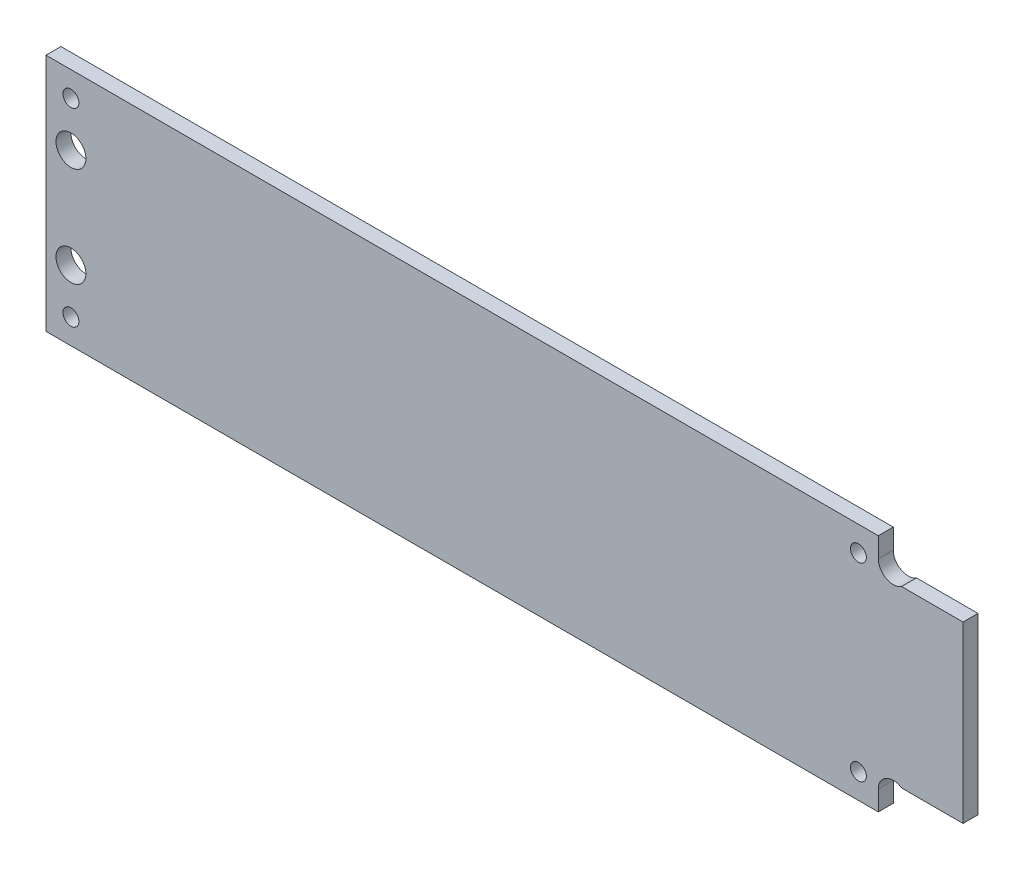
SolidWorks part; units mm, degrees
ref_plane "Top Plane" through (0, 0, 0) normal (0, 0, 1) x (1, 0, 0)
ref_plane "Right Plane" through (0, 0, 0) normal (0, 1, 0) x (1, 0, 0)
ref_plane "Front Plane" through (0, 0, 0) normal (1, 0, 0) x (0, 0, -1)
sketch "Sketch1" plane through (0, 0, 0) normal (0, 0, 1) x (1, 0, 0)
  line L8 (87.6583, -17.5) -> (100, -17.5)
  line L9 (100, -17.5) -> (100, 17.5)
  line L10 (100, 17.5) -> (87.6583, 17.5)
  line L11 (83, 20) -> (83, 24)
  line L12 (83, 24) -> (-84, 24)
  line L13 (-84, 24) -> (-84, -24)
  line L14 (-84, -24) -> (83, -24)
  line L15 (83, -24) -> (83, -20)
  line L16 (87.6583, -17.5) -> (100, -17.5)
  line L17 (100, -17.5) -> (100, 17.5)
  line L18 (100, 17.5) -> (87.6583, 17.5)
  line L19 (83, 20) -> (83, 24)
  line L20 (83, 24) -> (-84, 24)
  line L21 (-84, 24) -> (-84, -24)
  line L22 (-84, -24) -> (83, -24)
  line L23 (83, -24) -> (83, -20)
  line L36 (77, 10) -> (74, 10)
  line L37 (77, 15.5) -> (77, 10)
  line L38 (98, 15.5) -> (77, 15.5)
  line L39 (98, -15.5) -> (98, 15.5)
  line L40 (77, -15.5) -> (98, -15.5)
  line L41 (77, -10) -> (77, -15.5)
  line L42 (74, -10) -> (77, -10)
  line L43 (74, -20) -> (74, -10)
  line L44 (6, -21) -> (73, -21)
  line L45 (5, -19) -> (5, -20)
  line L46 (-5, -20) -> (-5, -19)
  line L47 (-73, -21) -> (-6, -21)
  line L48 (-74, 20) -> (-74, -20)
  line L49 (-6, 21) -> (-73, 21)
  line L50 (-5, 19) -> (-5, 20)
  line L51 (5, 20) -> (5, 19)
  line L52 (73, 21) -> (6, 21)
  line L53 (74, 10) -> (74, 20)
  line L54 (77, 10) -> (74, 10) construction
  line L55 (77, 15.5) -> (77, 10) construction
  line L56 (98, 15.5) -> (77, 15.5) construction
  line L57 (98, -15.5) -> (98, 15.5) construction
  line L58 (77, -15.5) -> (98, -15.5) construction
  line L59 (77, -10) -> (77, -15.5) construction
  line L60 (74, -10) -> (77, -10) construction
  line L61 (74, -20) -> (74, -10) construction
  line L62 (6, -21) -> (73, -21) construction
  line L63 (5, -19) -> (5, -20) construction
  line L64 (-5, -20) -> (-5, -19) construction
  line L65 (-73, -21) -> (-6, -21) construction
  line L66 (-74, 20) -> (-74, -20) construction
  line L67 (-6, 21) -> (-73, 21) construction
  line L68 (-5, 19) -> (-5, 20) construction
  line L69 (5, 20) -> (5, 19) construction
  line L70 (73, 21) -> (6, 21) construction
  line L71 (74, 10) -> (74, 20) construction
  circle A0 centre (-79, -19) radius 2.1 construction
  circle A1 centre (-79, -10) radius 3 construction
  arc A2 (87.6583, -17.5) -> (83, -20) centre (86, -20) ccw
  arc A3 (83, 20) -> (87.6583, 17.5) centre (86, 20) ccw
  arc A4 (87.6583, -17.5) -> (83, -20) centre (86, -20) ccw
  arc A5 (83, 20) -> (87.6583, 17.5) centre (86, 20) ccw
  circle A6 centre (-79, 10) radius 3 construction
  circle A7 centre (-79, 19) radius 2.1 construction
  circle A8 centre (-79, -19) radius 2.1 construction
  circle A9 centre (-79, -10) radius 3
  circle A10 centre (-79, 10) radius 3
  circle A11 centre (-79, 19) radius 2.1 construction
  circle A12 centre (79, -19) radius 2.1 construction
  circle A13 centre (79, 19) radius 2.1 construction
  arc A14 (73, -21) -> (74, -20) centre (73, -20) ccw
  arc A15 (5, -20) -> (6, -21) centre (6, -20) ccw
  arc A16 (5, -19) -> (-5, -19) centre (0, -19) ccw
  arc A17 (-6, -21) -> (-5, -20) centre (-6, -20) ccw
  arc A18 (-74, -20) -> (-73, -21) centre (-73, -20) ccw
  arc A19 (-73, 21) -> (-74, 20) centre (-73, 20) ccw
  arc A20 (-5, 20) -> (-6, 21) centre (-6, 20) ccw
  arc A21 (-5, 19) -> (5, 19) centre (0, 19) ccw
  arc A22 (6, 21) -> (5, 20) centre (6, 20) ccw
  arc A23 (74, 20) -> (73, 21) centre (73, 20) ccw
  arc A24 (73, -21) -> (74, -20) centre (73, -20) ccw construction
  arc A25 (5, -20) -> (6, -21) centre (6, -20) ccw construction
  arc A26 (5, -19) -> (-5, -19) centre (0, -19) ccw construction
  arc A27 (-6, -21) -> (-5, -20) centre (-6, -20) ccw construction
  arc A28 (-74, -20) -> (-73, -21) centre (-73, -20) ccw construction
  arc A29 (-73, 21) -> (-74, 20) centre (-73, 20) ccw construction
  arc A30 (-5, 20) -> (-6, 21) centre (-6, 20) ccw construction
  arc A31 (-5, 19) -> (5, 19) centre (0, 19) ccw construction
  arc A32 (6, 21) -> (5, 20) centre (6, 20) ccw construction
  arc A33 (74, 20) -> (73, 21) centre (73, 20) ccw construction
  circle A34 centre (0, -19) radius 2.1 construction
  circle A35 centre (0, 19) radius 2.1 construction
  circle A36 centre (79, -19) radius 2.1 construction
  circle A37 centre (79, 19) radius 2.1 construction
  circle A38 centre (0, -19) radius 2.1 construction
  circle A39 centre (0, 19) radius 2.1 construction
  dimension "D1" = 0
  dimension "D2" = 0
extrude "Boss-Extrude1" add sketch "Sketch1" along normal blind 3
sketch "Sketch2" plane through (0, 0, 0) normal (0, 0, -1) x (-1, 0, 0)
  line L18 (-7.4833, 18.5) -> (-71.5, 18.5)
  line L19 (-71.5, 18.5) -> (-71.5, 7.5)
  line L20 (-71.5, 7.5) -> (-79.5, 7.5)
  line L21 (-79.5, 7.5) -> (-79.5, 13)
  line L22 (-79.5, 13) -> (-95.5, 13)
  line L23 (-95.5, 13) -> (-95.5, -13)
  line L24 (-95.5, -13) -> (-79.5, -13)
  line L25 (-79.5, -13) -> (-79.5, -7.5)
  line L26 (-79.5, -7.5) -> (-71.5, -7.5)
  line L27 (-71.5, -7.5) -> (-71.5, -18.5)
  line L28 (-71.5, -18.5) -> (-7.4833, -18.5)
  line L29 (-7.4833, -18.5) -> (-7.4833, -18.5)
  line L30 (7.4833, -18.5) -> (7.4833, -18.5)
  line L31 (7.4833, -18.5) -> (71.5, -18.5)
  line L32 (71.5, -18.5) -> (71.5, 18.5)
  line L33 (71.5, 18.5) -> (7.4833, 18.5)
  line L34 (7.4833, 18.5) -> (7.4833, 18.5)
  line L35 (-7.4833, 18.5) -> (-7.4833, 18.5)
  line L36 (-73.5, 20) -> (-73.5, 9.5)
  line L37 (-73.5, 9.5) -> (-77.5, 9.5)
  line L38 (-77.5, 9.5) -> (-77.5, 15)
  line L39 (-77.5, 15) -> (-97.5, 15)
  line L40 (-97.5, 15) -> (-97.5, -15)
  line L41 (-97.5, -15) -> (-77.5, -15)
  line L42 (-77.5, -15) -> (-77.5, -9.5)
  line L43 (-77.5, -9.5) -> (-73.5, -9.5)
  line L44 (-73.5, -9.5) -> (-73.5, -20)
  line L45 (-73, -20.5) -> (-6, -20.5)
  line L46 (-5.5, -20) -> (-5.5, -19)
  line L47 (5.5, -19) -> (5.5, -20)
  line L48 (6, -20.5) -> (73, -20.5)
  line L49 (73.5, -20) -> (73.5, 20)
  line L50 (73, 20.5) -> (6, 20.5)
  line L51 (5.5, 20) -> (5.5, 19)
  line L52 (-5.5, 19) -> (-5.5, 20)
  line L53 (-6, 20.5) -> (-73, 20.5)
  line L54 (-73.5, 20) -> (-73.5, 9.5)
  line L55 (-73.5, 9.5) -> (-77.5, 9.5)
  line L56 (-77.5, 9.5) -> (-77.5, 15)
  line L57 (-77.5, 15) -> (-97.5, 15)
  line L58 (-97.5, 15) -> (-97.5, -15)
  line L59 (-97.5, -15) -> (-77.5, -15)
  line L60 (-77.5, -15) -> (-77.5, -9.5)
  line L61 (-77.5, -9.5) -> (-73.5, -9.5)
  line L62 (-73.5, -9.5) -> (-73.5, -20)
  line L63 (-73, -20.5) -> (-6, -20.5)
  line L64 (-5.5, -20) -> (-5.5, -19)
  line L65 (5.5, -19) -> (5.5, -20)
  line L66 (6, -20.5) -> (73, -20.5)
  line L67 (73.5, -20) -> (73.5, 20)
  line L68 (73, 20.5) -> (6, 20.5)
  line L69 (5.5, 20) -> (5.5, 19)
  line L70 (-5.5, 19) -> (-5.5, 20)
  line L71 (-6, 20.5) -> (-73, 20.5)
  arc A10 (-71.5, 18.5) -> (-71.5, 18.5) centre (-71.5, 18.5) ccw
  arc A11 (-71.5, -18.5) -> (-71.5, -18.5) centre (-71.5, -18.5) ccw
  arc A12 (-7.4833, -18.5) -> (-7.4833, -18.5) centre (-7.4833, -18.5) ccw
  arc A13 (7.4833, -18.5) -> (-7.4833, -18.5) centre (0, -19) ccw
  arc A14 (7.4833, -18.5) -> (7.4833, -18.5) centre (7.4833, -18.5) ccw
  arc A15 (71.5, -18.5) -> (71.5, -18.5) centre (71.5, -18.5) ccw
  arc A16 (71.5, 18.5) -> (71.5, 18.5) centre (71.5, 18.5) ccw
  arc A17 (7.4833, 18.5) -> (7.4833, 18.5) centre (7.4833, 18.5) ccw
  arc A18 (-7.4833, 18.5) -> (7.4833, 18.5) centre (0, 19) ccw
  arc A19 (-7.4833, 18.5) -> (-7.4833, 18.5) centre (-7.4833, 18.5) ccw
  arc A20 (-73, 20.5) -> (-73.5, 20) centre (-73, 20) ccw
  arc A21 (-73.5, -20) -> (-73, -20.5) centre (-73, -20) ccw
  arc A22 (-6, -20.5) -> (-5.5, -20) centre (-6, -20) ccw
  arc A23 (5.5, -19) -> (-5.5, -19) centre (0, -19) ccw
  arc A24 (5.5, -20) -> (6, -20.5) centre (6, -20) ccw
  arc A25 (73, -20.5) -> (73.5, -20) centre (73, -20) ccw
  arc A26 (73.5, 20) -> (73, 20.5) centre (73, 20) ccw
  arc A27 (6, 20.5) -> (5.5, 20) centre (6, 20) ccw
  arc A28 (-5.5, 19) -> (5.5, 19) centre (0, 19) ccw
  arc A29 (-5.5, 20) -> (-6, 20.5) centre (-6, 20) ccw
  arc A30 (-73, 20.5) -> (-73.5, 20) centre (-73, 20) ccw
  arc A31 (-73.5, -20) -> (-73, -20.5) centre (-73, -20) ccw
  arc A32 (-6, -20.5) -> (-5.5, -20) centre (-6, -20) ccw
  arc A33 (5.5, -19) -> (-5.5, -19) centre (0, -19) ccw
  arc A34 (5.5, -20) -> (6, -20.5) centre (6, -20) ccw
  arc A35 (73, -20.5) -> (73.5, -20) centre (73, -20) ccw
  arc A36 (73.5, 20) -> (73, 20.5) centre (73, 20) ccw
  arc A37 (6, 20.5) -> (5.5, 20) centre (6, 20) ccw
  arc A38 (-5.5, 19) -> (5.5, 19) centre (0, 19) ccw
  arc A39 (-5.5, 20) -> (-6, 20.5) centre (-6, 20) ccw
  dimension "D1" = 0.5
  dimension "D2" = 2
extrude "Boss-Extrude2" add sketch "Sketch2" along normal blind 2
chamfer "Chamfer1" distance 0.5 angle 45 28 edges at (39.5, 20.5, -2) (5.6464, 20.3536, -2) (5.5, 19.5, -2) (0, 13.5, -2) (-5.5, 19.5, -2) (-5.6464, 20.3536, -2) (-39.5, 20.5, -2) (-73.3536, 20.3536, -2) (-73.5, 0, -2) (-73.3536, -20.3536, -2) (-39.5, -20.5, -2) (-5.6464, -20.3536, -2) (-5.5, -19.5, -2) (0, -13.5, -2) (5.5, -19.5, -2) (5.6464, -20.3536, -2) (39.5, -20.5, -2) (73.3536, -20.3536, -2) (73.5, -14.75, -2) (75.5, -9.5, -2) (77.5, -12.25, -2) (87.5, -15, -2) (97.5, 0, -2) (87.5, 15, -2) (77.5, 12.25, -2) (75.5, 9.5, -2) (73.5, 14.75, -2) (73.3536, 20.3536, -2)
fillet "Fillet1" radius 1 16 edges at (-71.5, 0, 0) (-39.4917, -18.5, 0) (0, -11.5, 0) (39.4917, -18.5, 0) (71.5, -13, 0) (75.5, -7.5, 0) (79.5, -10.25, 0) (87.5, -13, 0) (95.5, 0, 0) (87.5, 13, 0) (79.5, 10.25, 0) (75.5, 7.5, 0) (71.5, 13, 0) (39.4917, 18.5, 0) (0, 11.5, 0) (-39.4917, 18.5, 0)
sketch "Sketch3" plane through (0, 0, 3) normal (0, 0, 1) x (1, 0, 0)
  circle A0 centre (-79, 19) radius 1.6
  circle A1 centre (-79, -19) radius 1.6
  circle A2 centre (79, 19) radius 1.6
  circle A3 centre (79, -19) radius 1.6
  dimension "D1" = 3.2
extrude "Cut-Extrude1" cut sketch "Sketch3" against normal through all
